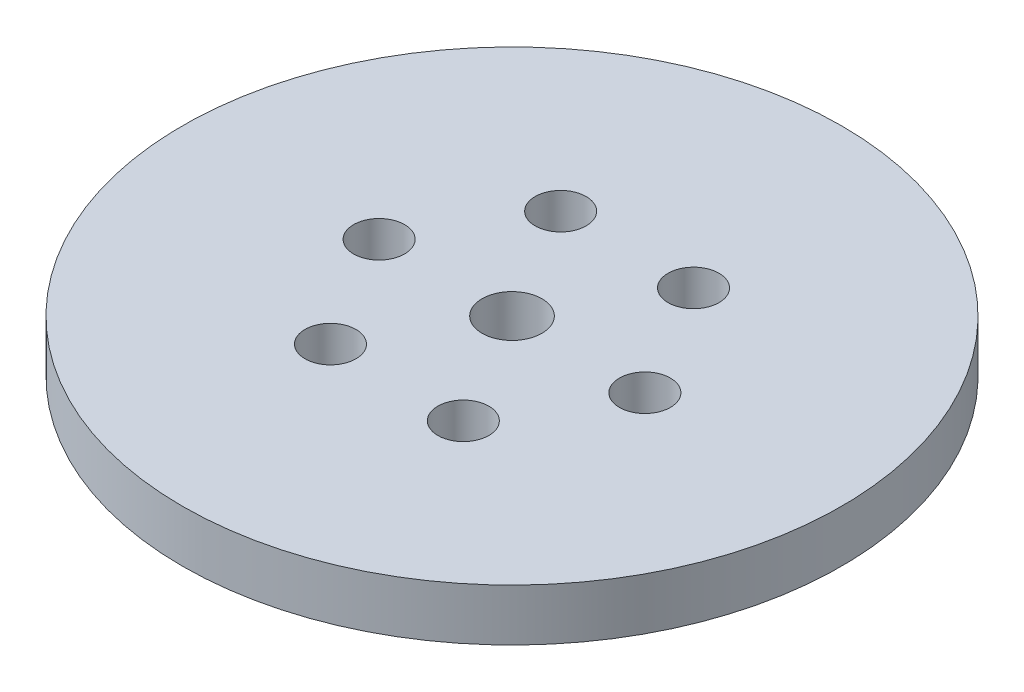
SolidWorks part; units mm, degrees
ref_plane "Front Plane" through (0, 0, 0) normal (0, 0, 1) x (1, 0, 0)
ref_plane "Top Plane" through (0, 0, 0) normal (0, 1, 0) x (1, 0, 0)
ref_plane "Right Plane" through (0, 0, 0) normal (1, 0, 0) x (0, 0, -1)
sketch "Sketch1" plane through (0, 0, 0) normal (0, 1, 0) x (1, 0, 0)
  circle A0 centre (0, 0) radius 82.5
  dimension "FLANGE_OD" = 165
extrude "Boss-Extrude1" add sketch "Sketch1" along normal blind 13
sketch "Sketch2" plane through (0, 0, 0) normal (0, 1, 0) x (1, 0, 0)
  circle A0 centre (0, 0) radius 7.5
  dimension "BORE_D" = 15
extrude "Cut-Extrude1" cut sketch "Sketch2" along normal through all
sketch "Sketch3" plane through (0, 13, 0) normal (0, 1, 0) x (1, 0, 0)
  circle A0 centre (0, 0) radius 33.2679 construction
  circle A1 centre (-33.2679, 0) radius 6.379
  dimension "BOLT_D" = 12.7579
  dimension "BOLT_PCD" = 66.5359
extrude "Cut-Extrude2" cut sketch "Sketch3" against normal blind 11.1536
pattern_circular "CirPattern1" count 6 over 360 about axis through (0, 0, 0) along (0, 1, 0) of "Cut-Extrude2"
